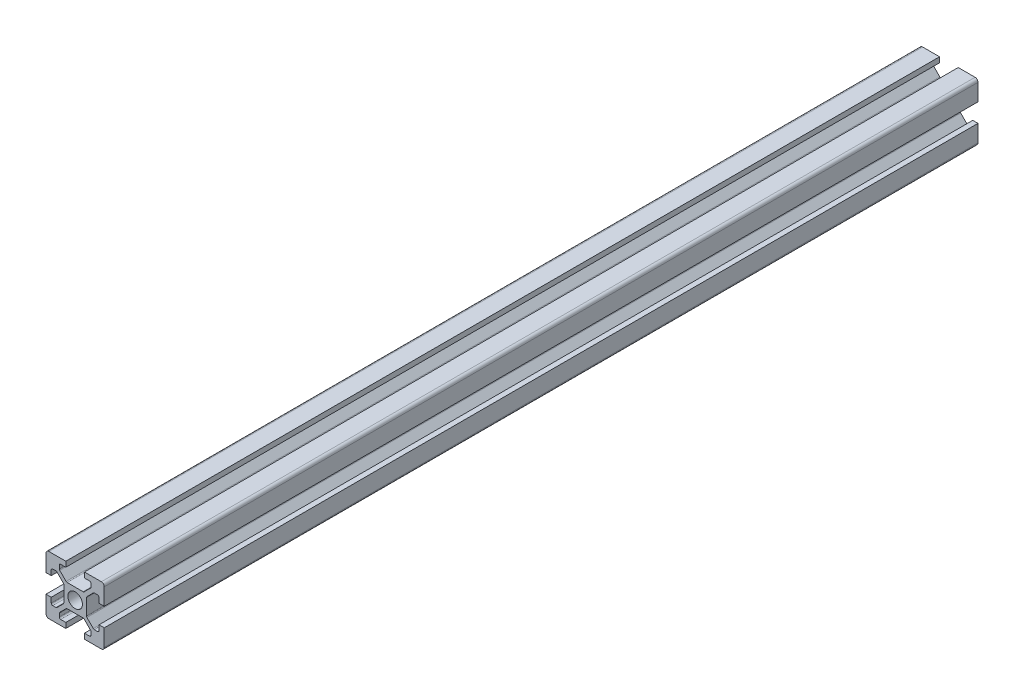
SolidWorks part; units mm, degrees
material "1060 Alloy"
ref_plane "Front Plane" through (0, 0, 0) normal (0, 0, 1) x (1, 0, 0)
ref_plane "Top Plane" through (0, 0, 0) normal (0, 1, 0) x (1, 0, 0)
ref_plane "Right Plane" through (0, 0, 0) normal (1, 0, 0) x (0, 0, -1)
sketch "Sketch1" plane through (0, 0, 0) normal (0, 0, 1) x (1, 0, 0)
  line L0 (20, 0) -> (-8.059, 28.059) construction
  line L1 (0, 0) -> (6.8, 0)
  line L2 (0, 0) -> (0, 6.8)
  line L3 (0, 20) -> (6.8, 20)
  line L4 (20, 0) -> (20, 6.8)
  line L5 (6.8, 20) -> (6.8, 18.2)
  line L6 (20, 20) -> (8.2322, 8.2322) construction
  line L7 (12.95, 6.1) -> (7.05, 6.1)
  line L8 (13.9, 7.05) -> (13.9, 12.95)
  line L9 (12.95, 13.9) -> (7.05, 13.9)
  line L10 (6.1, 7.05) -> (6.1, 12.95)
  line L11 (13.9, 6.1) -> (6.1, 13.9) construction
  line L12 (13.9, 13.9) -> (6.1, 6.1) construction
  line L13 (4.55, 16.4) -> (7.05, 13.9)
  line L14 (13.2, 18.2) -> (13.2, 20)
  line L15 (1.8, 6.8) -> (0, 6.8)
  line L16 (0, 13.2) -> (0, 20)
  line L17 (0, 13.2) -> (1.8, 13.2)
  line L18 (10, 10) -> (10, 13.9) construction
  line L19 (16.4, 4.55) -> (13.9, 7.05)
  line L20 (4.55, 16.4) -> (4.55, 18.2)
  line L21 (4.55, 18.2) -> (6.8, 18.2)
  line L22 (13.2, 18.2) -> (15.45, 18.2)
  line L23 (15.45, 18.2) -> (15.45, 16.4)
  line L24 (15.45, 16.4) -> (12.95, 13.9)
  line L25 (16.4, 4.55) -> (18.2, 4.55)
  line L26 (18.2, 4.55) -> (18.2, 6.8)
  line L27 (20, 6.8) -> (18.2, 6.8)
  line L28 (18.2, 13.2) -> (20, 13.2)
  line L29 (18.2, 13.2) -> (18.2, 15.45)
  line L30 (18.2, 15.45) -> (16.4, 15.45)
  line L31 (16.4, 15.45) -> (13.9, 12.95)
  line L32 (1.8, 4.55) -> (3.6, 4.55)
  line L33 (3.6, 15.45) -> (6.1, 12.95)
  line L34 (3.6, 15.45) -> (1.8, 15.45)
  line L35 (1.8, 15.45) -> (1.8, 13.2)
  line L36 (0, 13.2) -> (1.8, 13.2)
  line L37 (1.8, 6.8) -> (0, 6.8)
  line L38 (3.6, 4.55) -> (6.1, 7.05)
  line L39 (1.8, 6.8) -> (1.8, 4.55)
  line L40 (15.45, 3.6) -> (12.95, 6.1)
  line L41 (4.55, 3.6) -> (7.05, 6.1)
  line L42 (4.55, 1.8) -> (4.55, 3.6)
  line L43 (6.8, 1.8) -> (4.55, 1.8)
  line L44 (6.8, 1.8) -> (6.8, 0)
  line L45 (15.45, 3.6) -> (15.45, 1.8)
  line L46 (15.45, 1.8) -> (13.2, 1.8)
  line L47 (13.2, 0) -> (13.2, 1.8)
  line L48 (13.2, 20) -> (20, 20)
  line L49 (20, 13.2) -> (20, 20)
  line L50 (13.2, 0) -> (20, 0)
  line L51 (6.1, 6.1) -> (-5.5045, -5.5045) construction
  circle A0 centre (10, 10) radius 2.5
  point P25 (10, 16.4)
  point P39 (13.2, 19.1)
  point P46 (0.9, 6.8)
  dimension "D3" = 5
  dimension "D2" = 20
  dimension "D4" = 7.8
  dimension "D5" = 7.8
  dimension "D6" = 6.8
  dimension "D7" = 6.8
  dimension "D8" = 1.8
  dimension "D9" = 10.9
  dimension "D10" = 1.8
  dimension "D11" = 10.9
  dimension "D12" = 20
extrude "Boss-Extrude1" add sketch "Sketch1" along normal blind 300 contours L47 L50 L4 L27 L26 L25 L19 L8 L31 L30 L29 L28 L49 L48 L14 L22 L23 L24 L9 L13 L20 L21 L5 L3 L16 L17 L35 L34 L33 L10 L38 L32 L39 L15 L2 L1 L44 L43 L42 L41 L7 L40 L45 L46 A0 region at (0.2828, 3.4, 0)
fillet "Fillet1" radius 1 4 edges at (20, 20, 150) (20, 0, 150) (0, 0, 150) (0, 20, 150)
fillet "Fillet2" radius 0.5 6 edges at (4.55, 18.2, 150) (4.55, 16.4, 150) (7.05, 13.9, 150) (15.45, 18.2, 150) (15.45, 16.4, 150) (12.95, 13.9, 150)
fillet "Fillet3" radius 0.5 6 edges at (18.2, 15.45, 150) (16.4, 15.45, 150) (13.9, 12.95, 150) (18.2, 4.55, 150) (13.9, 7.05, 150) (16.4, 4.55, 150)
fillet "Fillet4" radius 0.5 6 edges at (1.8, 15.45, 150) (3.6, 15.45, 150) (6.1, 12.95, 150) (3.6, 4.55, 150) (1.8, 4.55, 150) (6.1, 7.05, 150)
fillet "Fillet5" radius 0.5 6 edges at (7.05, 6.1, 150) (4.55, 3.6, 150) (4.55, 1.8, 150) (15.45, 1.8, 150) (15.45, 3.6, 150) (12.95, 6.1, 150)
